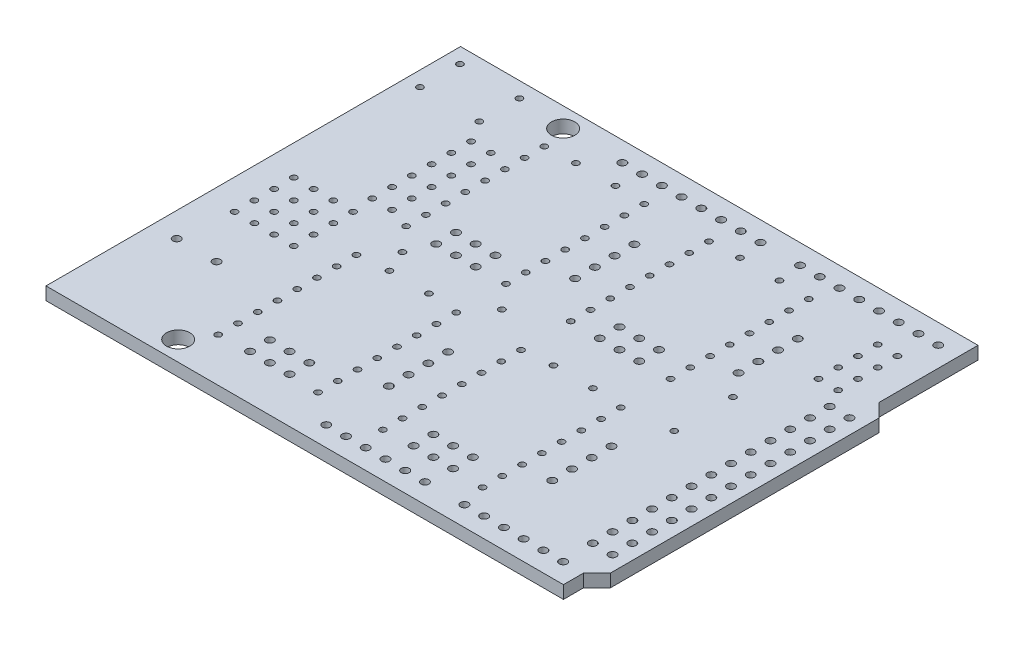
SolidWorks part; units mm, degrees
ref_plane "Front Plane" through (0, 0, 0) normal (0, 0, 1) x (1, 0, 0)
ref_plane "Top Plane" through (0, 0, 0) normal (0, 1, 0) x (1, 0, 0)
ref_plane "Right Plane" through (0, 0, 0) normal (1, 0, 0) x (0, 0, -1)
sketch "Sketch2" plane through (0, 0, 0) normal (0, 1, 0) x (1, 0, 0)
  line L1 (0, 0) -> (68.31, 0)
  line L2 (0, 0) -> (0, 53.34)
  line L3 (0, 53.34) -> (68.31, 53.34)
  line L4 (68.31, 0) -> (68.31, 53.34)
  dimension "D1" = 53.34
  dimension "D2" = 68.31
extrude "Boss-Extrude1" add sketch "Sketch2" along normal blind 1.65
sketch "Sketch3" plane through (0, 1.65, 0) normal (0, 1, 0) x (1, 0, 0)
  line L0 (0, 0) -> (68.31, 0) construction
  line L2 (68.31, 0) -> (68.31, 53.34) construction
  circle A0 centre (64, 2.54) radius 0.5
  dimension "D1" = 1
  dimension "D2" = 2.54
  dimension "D3" = 4.31
extrude "Cut-Extrude1" cut sketch "Sketch3" against normal through all
sketch "Sketch4" plane through (0, 1.65, 0) normal (0, 1, 0) x (1, 0, 0)
  line L0 (68.31, 53.34) -> (0, 53.34) construction
  circle A1 centre (64, 50.8) radius 0.5
  dimension "D2" = 1
  dimension "D3" = 2.54
extrude "Cut-Extrude2" cut sketch "Sketch4" against normal through all
sketch "Sketch5" plane through (0, 1.65, 0) normal (0, 1, 0) x (1, 0, 0)
  line L0 (0, 53.34) -> (0, 0) construction
  line L1 (0, 0) -> (68.31, 0) construction
  circle A0 centre (16.52, 5.64) radius 0.4
  circle A1 centre (29.36, 5.64) radius 0.4
  circle A2 centre (16.52, 29.82) radius 0.4
  circle A3 centre (29.36, 29.82) radius 0.4
  circle A4 centre (37.7, 29.82) radius 0.4
  circle A5 centre (50.54, 29.82) radius 0.4
  circle A6 centre (50.54, 5.64) radius 0.4
  circle A7 centre (37.7, 5.64) radius 0.4
  dimension "D1" = 0.8
  dimension "D2" = 16.52
  dimension "D3" = 5.64
  dimension "D4" = 12.84
  dimension "D5" = 24.18
  dimension "D6" = 8.34
  dimension "D7" = 12.84
extrude "Cut-Extrude3" cut sketch "Sketch5" against normal through all
pattern_linear "LPattern4" count 8 spacing 2.54 along (0, 0, -1) of "Cut-Extrude3"
pattern_linear "LPattern5" count 17 spacing 2.54 along (-1, 0, 0) skipping (8, 0) of "Cut-Extrude2"
pattern_linear "LPattern6" count 13 spacing 2.54 along (-1, 0, 0) skipping (6, 0) of "Cut-Extrude1"
sketch "Sketch6" plane through (0, 1.65, 0) normal (0, 1, 0) x (1, 0, 0)
  circle A0 centre (11.5, 20.39) radius 0.4
  dimension "D1" = 0.8
  dimension "D2" = 11.5
  dimension "D3" = 20.39
extrude "Cut-Extrude4" cut sketch "Sketch6" against normal through all
pattern_linear "LPattern7" count 4 spacing 2.54 along (0, 0, -1) count 4 spacing 2.54 along (-1, 0, 0) of "Cut-Extrude4"
sketch "Sketch7" plane through (0, 1.65, 0) normal (0, 1, 0) x (1, 0, 0)
  circle A0 centre (8.2698, 13.67) radius 0.5
  circle A1 centre (3.1498, 13.67) radius 0.5
  dimension "D1" = 1
  dimension "D2" = 1
  dimension "D3" = 5.12
  dimension "D4" = 13.67
extrude "Cut-Extrude5" cut sketch "Sketch7" against normal through all
sketch "Sketch8" plane through (0, 1.65, 0) normal (0, 1, 0) x (1, 0, 0)
  circle A0 centre (11.25, 30.74) radius 0.4
  dimension "D1" = 0.8
  dimension "D2" = 11.25
  dimension "D3" = 30.74
extrude "Cut-Extrude6" cut sketch "Sketch8" against normal through all
pattern_linear "LPattern8" count 6 spacing 2.54 along (0, 0, -1) count 2 spacing 2.54 along (1, 0, 0) of "Cut-Extrude6"
sketch "Sketch9" plane through (0, 1.65, 0) normal (0, 1, 0) x (1, 0, 0)
  circle A0 centre (20.43, 32.32) radius 0.5
  circle A1 centre (20.43, 8.37) radius 0.5
  circle A2 centre (41.47, 8.37) radius 0.5
  circle A3 centre (41.47, 32.32) radius 0.5
  dimension "D1" = 1
  dimension "D2" = 20.43
  dimension "D3" = 8.37
  dimension "D4" = 23.95
  dimension "D5" = 21.04
extrude "Cut-Extrude7" cut sketch "Sketch9" against normal through all
pattern_linear "LPattern9" count 3 spacing 2.54 along (1, 0, 0) count 2 spacing 2.54 along (0, 0, 1) of "Cut-Extrude7"
sketch "Sketch10" plane through (0, 1.65, 0) normal (0, 1, 0) x (1, 0, 0)
  circle A0 centre (33.22, 34.86) radius 0.5
  circle A1 centre (33.22, 10.89) radius 0.5
  circle A2 centre (54.25, 10.89) radius 0.5
  circle A3 centre (54.25, 34.86) radius 0.5
  dimension "D1" = 1
  dimension "D2" = 10.89
  dimension "D3" = 33.22
  dimension "D4" = 23.97
  dimension "D5" = 21.03
extrude "Cut-Extrude8" cut sketch "Sketch10" against normal through all
pattern_linear "LPattern10" count 4 spacing 2.54 along (0, 0, -1) of "Cut-Extrude8"
sketch "Sketch11" plane through (0, 1.65, 0) normal (0, 1, 0) x (1, 0, 0)
  circle A0 centre (20.41, 23.78) radius 0.4
  circle A1 centre (20.41, 47.78) radius 0.4
  circle A2 centre (41.51, 47.78) radius 0.4
  circle A3 centre (41.51, 23.78) radius 0.4
  dimension "D1" = 0.8
  dimension "D2" = 41.51
  dimension "D3" = 23.78
  dimension "D4" = 21.1
  dimension "D5" = 24
extrude "Cut-Extrude9" cut sketch "Sketch11" against normal through all
pattern_linear "LPattern11" count 2 spacing 5.08 along (1, 0, 0) of "Cut-Extrude9"
sketch "Sketch12" plane through (0, 1.65, 0) normal (0, 1, 0) x (1, 0, 0)
  line L0 (68.31, 0) -> (68.31, 53.34) construction
  line L1 (0, 0) -> (68.31, 0) construction
  circle A0 centre (9.56, 46.2) radius 0.4
  circle A1 centre (9.56, 51.35) radius 0.4
  circle A2 centre (1.91, 51.35) radius 0.4
  circle A3 centre (1.91, 46.2) radius 0.4
  circle A4 centre (19.16, 26.7) radius 0.4
  circle A5 centre (31.96, 26.7) radius 0.4
  circle A6 centre (56.58, 24.26) radius 0.4
  circle A7 centre (56.58, 31.81) radius 0.4
  dimension "D1" = 0.8
  dimension "D2" = 7.65
  dimension "D3" = 46.2
  dimension "D4" = 9.56
  dimension "D5" = 5.15
  dimension "D6" = 19.16
  dimension "D7" = 26.7
  dimension "D8" = 12.8
  dimension "D9" = 24.26
  dimension "D10" = 11.73
  dimension "D11" = 7.55
extrude "Cut-Extrude10" cut sketch "Sketch12" against normal through all
sketch "Sketch13" plane through (0, 1.65, 0) normal (0, 1, 0) x (1, 0, 0)
  line L0 (68.31, 0) -> (68.31, 53.34) construction
  line L1 (0, 0) -> (68.31, 0) construction
  circle A0 centre (63.86, 6.5) radius 0.5
  dimension "D1" = 1
  dimension "D2" = 4.45
  dimension "D3" = 6.5
extrude "Cut-Extrude11" cut sketch "Sketch13" against normal through all
pattern_linear "LPattern12" count 13 spacing 2.54 along (0, 0, -1) count 2 spacing 2.54 along (1, 0, 0) of "Cut-Extrude11"
sketch "Sketch14" plane through (0, 1.65, 0) normal (0, 1, 0) x (1, 0, 0)
  line L0 (68.31, 53.34) -> (0, 53.34) construction
  line L1 (68.31, 0) -> (68.31, 53.34) construction
  circle A0 centre (60.05, 39.34) radius 0.4
  dimension "D1" = 0.8
  dimension "D2" = 14
  dimension "D3" = 8.26
extrude "Cut-Extrude12" cut sketch "Sketch14" against normal through all
pattern_linear "LPattern13" count 4 spacing 2.54 along (0, 0, -1) count 2 spacing 2.54 along (1, 0, 0) of "Cut-Extrude12"
sketch "Sketch15" plane through (0, 1.65, 0) normal (0, 1, 0) x (1, 0, 0)
  line L1 (68.31, 53.34) -> (0, 53.34) construction
  line L2 (66.58, 40.57) -> (66.58, 53.34)
  line L3 (66.58, 53.34) -> (68.31, 53.34)
  line L4 (68.31, 53.34) -> (68.31, 38.84)
  line L5 (68.31, 0) -> (68.31, 53.34) construction
  line L6 (68.31, 38.84) -> (66.58, 40.57)
  line L7 (66.58, 0) -> (66.58, 2.57)
  line L8 (0, 0) -> (68.31, 0) construction
  line L9 (66.58, 2.57) -> (68.31, 4.3)
  line L10 (68.31, 4.3) -> (68.31, 0)
  line L11 (68.31, 0) -> (66.58, 0)
  circle A0 centre (15.74, 50.8) radius 1.5
  circle A1 centre (14.47, 2.54) radius 1.5
  circle A6 centre (14.47, 2.54) radius 1.5 construction
  circle A7 centre (15.74, 50.8) radius 1.5 construction
  dimension "D1" = 3
  dimension "D2" = 3
  dimension "D6" = 45
  dimension "D7" = 14.5
  dimension "D8" = 1.73
  dimension "D9" = 4.3
extrude "Cut-Extrude13" cut sketch "Sketch15" against normal through all
equation "\"D7@Sketch5\"=\"D4@Sketch5\""
